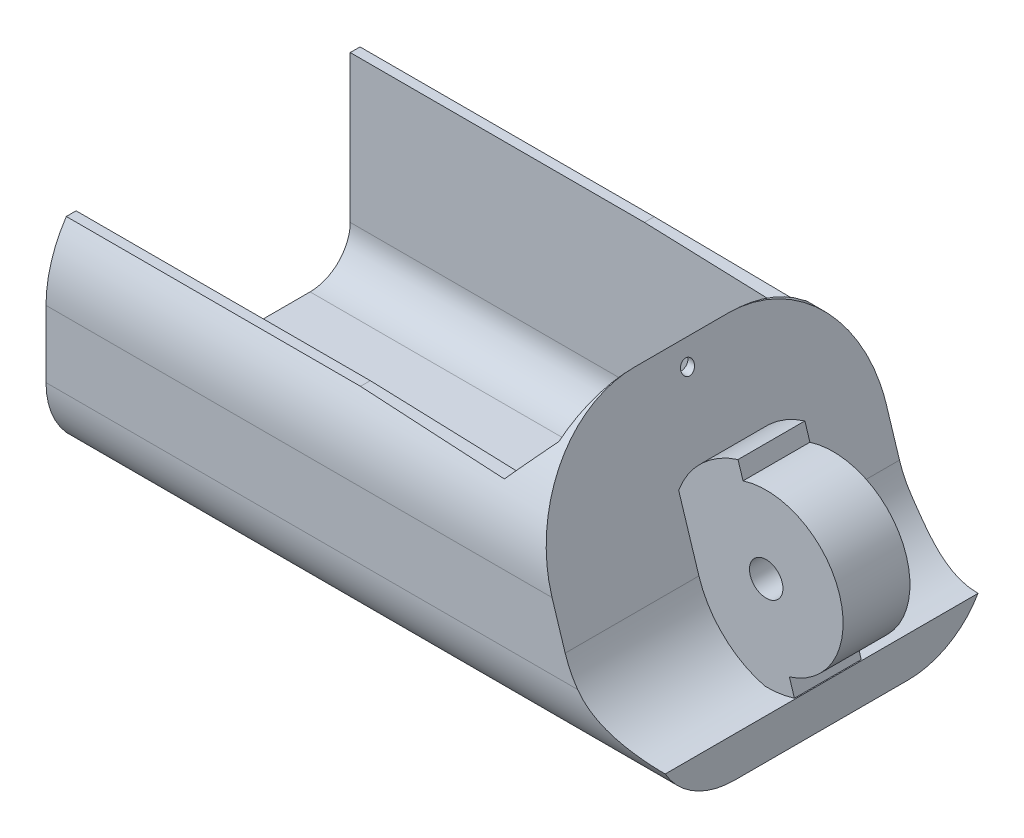
SolidWorks part; units mm, degrees
ref_plane "Alzado" through (0, 0, 0) normal (0, 0, 1) x (1, 0, 0)
ref_plane "Planta" through (0, 0, 0) normal (0, 1, 0) x (1, 0, 0)
ref_plane "Vista lateral" through (0, 0, 0) normal (1, 0, 0) x (0, 0, -1)
sketch "Croquis1" plane through (0, 0, 0) normal (0, 0, 1) x (1, 0, 0)
  line L1 (-52.5, -20) -> (52.5, -20)
  line L2 (-52.5, -20) -> (-52.5, 20)
  line L3 (-52.5, 20) -> (52.5, 20)
  line L4 (52.5, -20) -> (52.5, 20)
  line L5 (-52.5, -20) -> (52.5, 20) construction
  line L6 (-52.5, 20) -> (52.5, -20) construction
  point P0 (0, 0)
  dimension "D1" = 105
  dimension "D2" = 40
extrude "Saliente-Extruir1" add sketch "Croquis1" along normal mid plane 50
sketch "Croquis2" plane through (0, 0, 25) normal (0, 0, 1) x (1, 0, 0)
  line L0 (-52.5, 12) -> (-46.5, 12)
  line L1 (-52.5, 20) -> (-52.5, -20) construction
  line L2 (-46.5, 12) -> (-46.5, 6)
  line L3 (-46.5, 6) -> (-26.5, 6)
  line L4 (-26.5, 6) -> (-26.5, 12)
  line L5 (-26.5, 12) -> (-8.5, 12)
  line L6 (-8.5, 12) -> (-8.5, 6)
  line L7 (-8.5, 6) -> (13.5, 6)
  line L8 (13.5, 6) -> (13.5, 11.2419)
  line L9 (13.5, 11.2419) -> (17.5, 16)
  line L10 (17.5, 16) -> (17.5, 20)
  line L11 (52.5, 20) -> (-52.5, 20) construction
  line L12 (-52.5, 12) -> (-52.5, 20)
  line L13 (-52.5, 20) -> (17.5, 20)
  line L14 (-52.5, -20) -> (52.5, -20) construction
  line L15 (39.5, 0) -> (0, 0) construction
  line L16 (52.5, -20) -> (52.5, 20) construction
  line L17 (-46.5, 12) -> (-26.5, 12)
  line L18 (-8.5, 12) -> (13.5, 11.2419)
  line L19 (-46.5, 12) -> (-26.5, 12)
  circle A0 centre (39.5, 0) radius 13 construction
  point P4 (17.5, 18)
  line M14 (52.5, 20) -> (-52.5, 20)
  line M15 (-52.5, 20) -> (-52.5, -20)
  dimension "D10" = 26
  dimension "D1" = 6
  dimension "D2" = 70
  dimension "D3" = 18
  dimension "D4" = 20
  dimension "D5" = 6
  dimension "D6" = 26
  dimension "D7" = 4
  dimension "D8" = 4
  dimension "D9" = 4.7581
extrude "Cortar-Extruir1" cut sketch "Croquis2" against normal blind 50 contours L5 L18 L9 L10 L0 L17 M14 M15 region at (-17.5408, 15.967, 25)
sketch "Croquis5" plane through (0, 0, 25) normal (0, 0, 1) x (1, 0, 0)
  line L0 (-21.8249, 0) -> (71.7691, 0) construction
  line L1 (52.5, -20) -> (17.5, -20) construction
  line L2 (52.5, 0) -> (52.5, 20) construction
  line L3 (52.5, 20) -> (17.5, 20) construction
  line L4 (17.5, -20) -> (17.5, 20) construction
  line L5 (17.5, 20) -> (25.1503, -4.2172)
  line L6 (17.5, 20) -> (52.5, 20)
  line L7 (52.5, 20) -> (52.5, 0)
  line L9 (52.5, -20) -> (30.1361, -20)
  line L10 (52.5, -20) -> (52.5, 20) construction
  line L11 (38.5, -14) -> (52.5, -14)
  line L12 (52.5, -14) -> (52.5, 0)
  arc A0 (52.5, 0) -> (38.5, -14) centre (38.5, 0) ccw
  arc A1 (38.5, -14) -> (52.5, 0) centre (38.5, 0) ccw
  line M2 (52.5, 20) -> (17.5, 20)
  line M15 (52.5, -20) -> (52.5, 20)
  dimension "D1" = 28
extrude "Cortar-Extruir2" cut sketch "Croquis5" against normal blind 50 contours A0 L5 M15 M2 | A0 region at (34.6505, 14.3929, 25) region at (38.5, 0, 25)
sketch "Croquis6" plane through (0, 0, 0) normal (0, 0, 1) x (1, 0, 0)
  line L0 (30.0802, 16.6941) -> (40.1499, -15.1819) construction
  line L1 (17.5, 20) -> (25.1503, -4.2172) construction
  line L2 (38.6808, -10.5315) -> (39.4339, -12.9154)
  line L3 (31.7525, 11.4002) -> (30.9995, 13.784)
  circle A0 centre (35.2167, 0.4343) radius 14
  circle A1 centre (35.2167, 0.4343) radius 11.5
  circle A2 centre (35.2167, 0.4343) radius 2.5
  dimension "D1" = 28
  dimension "D3" = 23
  dimension "D5" = 5
  dimension "D2" = 11
  dimension "D4" = 35.2167
extrude "Saliente-Extruir3" add sketch "Croquis6" along normal mid plane 10 contours A1 L0 A2 | L0 A1 A2 | A1 L3 A0 L2 region at (23.9375, -3.1288, 0) region at (40.0514, 1.9616, 0) region at (30.3819, -1.093, 0)
sketch "Croquis8" plane through (0, 0, 25) normal (0, 0, 1) x (1, 0, 0)
  line L1 (-52.5, -20) -> (52.5, -20) construction
  line L2 (38.5, -20) -> (38.5, -14)
  line L8 (17.5, 20) -> (17.5, 16)
  line L9 (17.5, 16) -> (13.5, 11.2419)
  line L13 (-8.5, 12) -> (-52.5, 12)
  line L14 (13.5, 11.2419) -> (-8.5, 12)
  line L15 (13.5, 11.2419) -> (-8.5, 12)
  line L16 (25.1503, -4.2172) -> (17.5, 20)
  line L27 (-52.5, 12) -> (-52.5, -20)
  line L28 (-52.5, -20) -> (52.5, -20)
  line L29 (52.5, -20) -> (52.5, 0)
  line L42 (38.5, -20) -> (52.5, -20)
  line L43 (52.5, -20) -> (52.5, 0)
  arc A2 (25.1503, -4.2172) -> (52.5, 0) centre (38.5, 0) ccw
  arc A4 (38.5, -14) -> (52.5, 0) centre (38.5, 0) ccw
  line M30 (-52.5, -20) -> (52.5, -20)
  line M31 (52.5, -20) -> (52.5, 0)
  arc M32 (52.5, 0) -> (25.1503, -4.2172) centre (38.5, 0) cw
  dimension "D1" = 0
extrude "Cortar-Extruir3" cut sketch "Croquis8" against normal through all contours L2 M30 M31 M32 region at (46.7922, -14.9556, 25)
fillet "Redondeo2" radius 12 2 edges at (-7, -20, -25) (-7, -20, 25)
sketch "Croquis10" plane through (-52.5, 0, 0) normal (-1, 0, 0) x (0, 0, 1)
  line L0 (-25, 12) -> (-25, -8) construction
  line L1 (-25, 32) -> (25, 32)
  line L2 (-25, 32) -> (-25, 0)
  line L3 (-25, 0) -> (25, 0)
  line L4 (25, 32) -> (25, 0)
  line L5 (25, 12) -> (25, -8) construction
  line L8 (-25, 0) -> (-25, 2)
  line L9 (-7, 20) -> (7, 20)
  line L10 (25, 0) -> (25, 2)
  line L11 (-21.9512, -17.561) -> (25, 20) construction
  line L12 (-25, 20) -> (21.9512, -17.561) construction
  line L13 (-25, 12) -> (25, 12) construction
  line L14 (-25, 20) -> (25, 20) construction
  arc A1 (7, 20) -> (25, 2) centre (7, 2) cw
  arc A2 (-25, 2) -> (-7, 20) centre (-7, 2) cw
  point P8 (0, 12)
  line M15 (-25, 12) -> (-25, -8)
  line M20 (25, 12) -> (-25, 12)
  dimension "D1" = 18
  dimension "D2" = 32
extrude "Cortar-Extruir4" cut sketch "Croquis10" against normal blind 110 contours A2 M15 M20 | A2 L9 A1 L4 L1 L2 M20 | A1 L4 M20 region at (-52.5, 24.5091, 0) region at (-52.5, 9.5441, -24.1048) region at (-52.5, 9.5441, 24.1048)
sketch "Croquis11" plane through (-52.5, 0, 0) normal (-1, 0, 0) x (0, 0, 1)
  line L0 (0, 9.5473) -> (0, -17.1641) construction
  line L1 (-20.5, 23.7724) -> (20.5, 23.7724)
  line L2 (-20.5, 23.7724) -> (-20.5, -10)
  line L3 (-14.5, -16) -> (14.5, -16)
  line L4 (20.5, 23.7724) -> (20.5, -10)
  line L5 (13, -20) -> (-13, -20) construction
  arc A0 (14.5, -16) -> (20.5, -10) centre (14.5, -10) ccw
  arc A1 (-20.5, -10) -> (-14.5, -16) centre (-14.5, -10) ccw
  point P9 (20.5, -16)
  point P12 (-20.5, -16)
  line M10 (21.9666, 12) -> (-21.9666, 12)
  dimension "D2" = 6
  dimension "D1" = 41
  dimension "D3" = 4
  dimension "D4" = 33.7724
extrude "Cortar-Extruir5" cut sketch "Croquis11" against normal blind 66 contours L2 A1 L3 A0 L4 M10 | L4 L1 L2 M10 region at (-52.5, 17.8862, 0) region at (-52.5, -1.8273, 0)
sketch "Croquis12" plane through (0, 0, 0) normal (0, 0, 1) x (1, 0, 0)
  line L4 (-52.5, -28) -> (-32.5, -28)
  line L12 (-50.1656, -23) -> (-34.8344, -23)
  line L21 (-50.1656, -23) -> (-50.1656, -26)
  line L22 (-50.1656, -26) -> (-34.8344, -26)
  line L23 (-34.8344, -23) -> (-34.8344, -26)
  line L24 (-32.5, -20) -> (-32.5, -28)
  line L25 (-52.5, -20) -> (-32.5, -20)
  line L26 (-52.5, -20) -> (-52.5, -28)
  line L27 (38.5, -20) -> (-52.5, -20) construction
  line L28 (38.5, -20) -> (-52.5, -20)
  line L29 (-52.5, -8) -> (-52.5, -20) construction
  line L30 (-20.5, -35.1473) -> (-20.5, -3.279) construction
  line L31 (11.5, -20) -> (11.5, -28)
  line L32 (11.5, -20) -> (-8.5, -20)
  line L33 (-8.5, -20) -> (-8.5, -28)
  line L34 (-6.1656, -23) -> (-6.1656, -26)
  line L35 (9.1656, -26) -> (-6.1656, -26)
  line L36 (9.1656, -23) -> (9.1656, -26)
  line L37 (9.1656, -23) -> (-6.1656, -23)
  line L38 (11.5, -28) -> (-8.5, -28)
  spline S0 degree 2 poles (-32.5, -24) (-20.5, -16) (-8.5, -24) knots 0 0 0 1 1 1
  dimension "D1" = 3
  dimension "D2" = 3
  dimension "D3" = 20
  dimension "D4" = 32
  dimension "D5" = 2
  dimension "D6" = 2.3344
  dimension "D7" = 2.3344
  dimension "D8" = 2.3344
  dimension "D9" = 2.3344
extrude "Saliente-Extruir4" add sketch "Croquis12" along normal mid plane 5 contours L25 L26 L4 L24 L12 L23 L22 L21 | L38 L31 L28 L33 L37 L36 L35 L34 | L24 S0 L28 | L28 S0 L33
sketch "Croquis13" plane through (17.5, 0, 0) normal (-1, 0, 0) x (0, 0, 1)
  line L0 (0, -4.4034) -> (0, 22.2086) construction
  circle A0 centre (0, 17) radius 1
  point P5 (0, 17.5577)
  dimension "D1" = 2
  dimension "D2" = 17
extrude "Cortar-Extruir6" cut sketch "Croquis13" against normal blind 10
fillet "Redondeo3" radius 2 4 edges at (-8.5, -28, 0) (-52.5, -28, 0) (-32.5, -28, 0) (11.5, -28, 0)
fillet "Redondeo4" radius 2 1 edges at (11.5, -20, 0)
fillet "Redondeo5" radius 1 8 edges at (-34.8344, -26, 0) (-50.1656, -26, 0) (-50.1656, -23, 0) (-34.8344, -23, 0) (-6.1656, -26, 0) (-6.1656, -23, 0) (9.1656, -26, 0) (9.1656, -23, 0)
